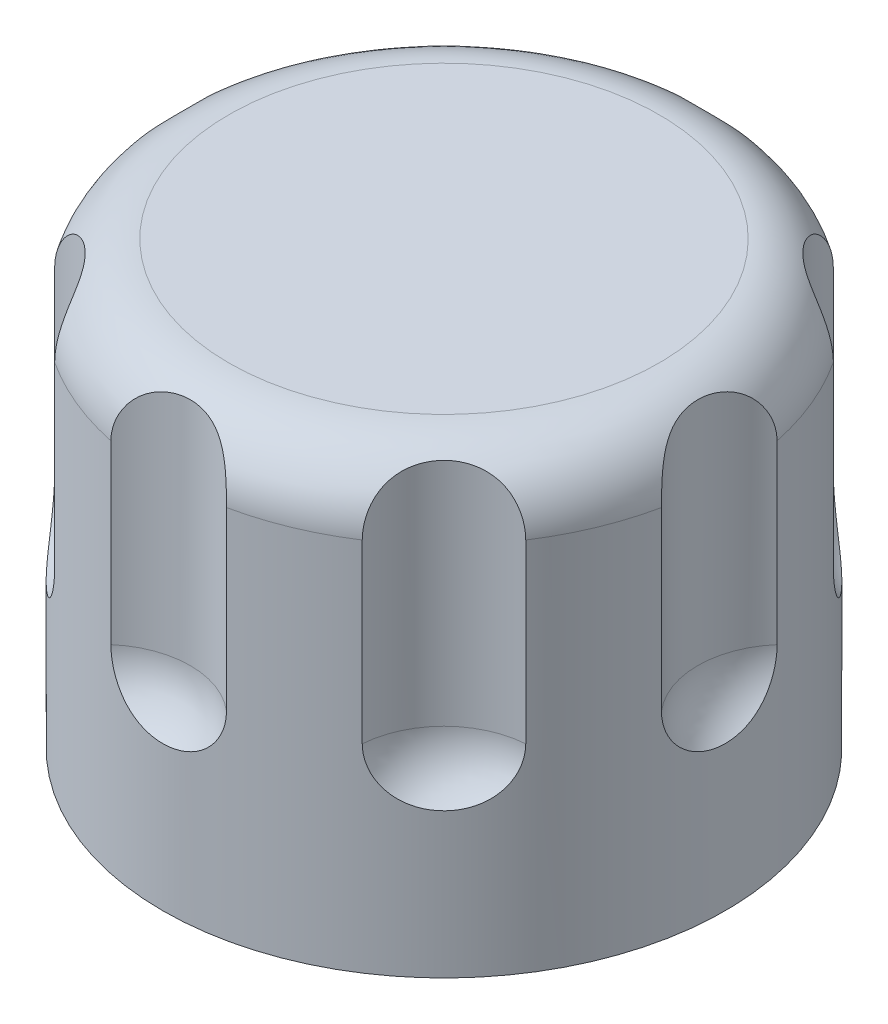
SolidWorks part; units mm, degrees
ref_plane "Front Plane" through (0, 0, 0) normal (0, 0, 1) x (1, 0, 0)
ref_plane "Top Plane" through (0, 0, 0) normal (0, 1, 0) x (1, 0, 0)
ref_plane "Right Plane" through (0, 0, 0) normal (1, 0, 0) x (0, 0, -1)
sketch "Sketch1" plane through (0, 0, 0) normal (0, 1, 0) x (1, 0, 0)
  circle A0 centre (0, 0) radius 12.75
  dimension "D1" = 25.5
extrude "Boss-Extrude1" add sketch "Sketch1" along normal blind 20
sketch "Sketch2" plane through (0, 0, 0) normal (0, -1, 0) x (1, 0, 0)
  circle A0 centre (0, 0) radius 3.05
  dimension "D1" = 6.1
extrude "Cut-Extrude1" cut sketch "Sketch2" against normal blind 18.3 and the other way through all
sketch "Sketch3" plane through (0, 0, 0) normal (0, -1, 0) x (1, 0, 0)
  circle A0 centre (0, 0) radius 3.5
  dimension "D1" = 7
extrude "Cut-Extrude2" cut sketch "Sketch3" against normal blind 6
fillet "Fillet1" radius 3 1 edges at (0, 20, 12.75)
sketch "Sketch5" plane through (0, 20, 0) normal (0, 1, 0) x (1, 0, 0)
  circle A2 centre (0, 15.5) radius 4
  circle A3 centre (0, 0) radius 12.75 construction
  circle A4 centre (10.9602, 10.9602) radius 4
  circle A5 centre (15.5, 0) radius 4
  circle A6 centre (10.9602, -10.9602) radius 4
  circle A7 centre (0, -15.5) radius 4
  circle A8 centre (-10.9602, -10.9602) radius 4
  circle A9 centre (-15.5, 0) radius 4
  circle A10 centre (-10.9602, 10.9602) radius 4
  point P20 (0, 0)
  dimension "D1" = 8
  dimension "D3" = 0
  dimension "D5" = 0
  dimension "D2" = 15.5
  dimension "D4" = 8
extrude "Cut-Extrude3" cut sketch "Sketch5" against normal blind 14
fillet "Fillet3" radius 3 8 edges at (0, 6, 11.5) (-8.1317, 6, 8.1317) (-11.5, 6, 0) (-8.1317, 6, -8.1317) (0, 6, -11.5) (8.1317, 6, -8.1317) (11.5, 6, 0) (8.1317, 6, 8.1317)
sketch "Sketch6" plane through (0, 18.3, 0) normal (0, -1, 0) x (1, 0, 0)
  line L0 (1.6, 2.5966) -> (1.6, -2.5966)
  circle A0 centre (0, 0) radius 3.05 construction
  circle A1 centre (0, 0) radius 3.05 construction
  arc A2 (1.6, -2.5966) -> (1.6, 2.5966) centre (0, 0) ccw
  dimension "D1" = 1.6
extrude "Boss-Extrude2" add sketch "Sketch6" along normal blind 10
